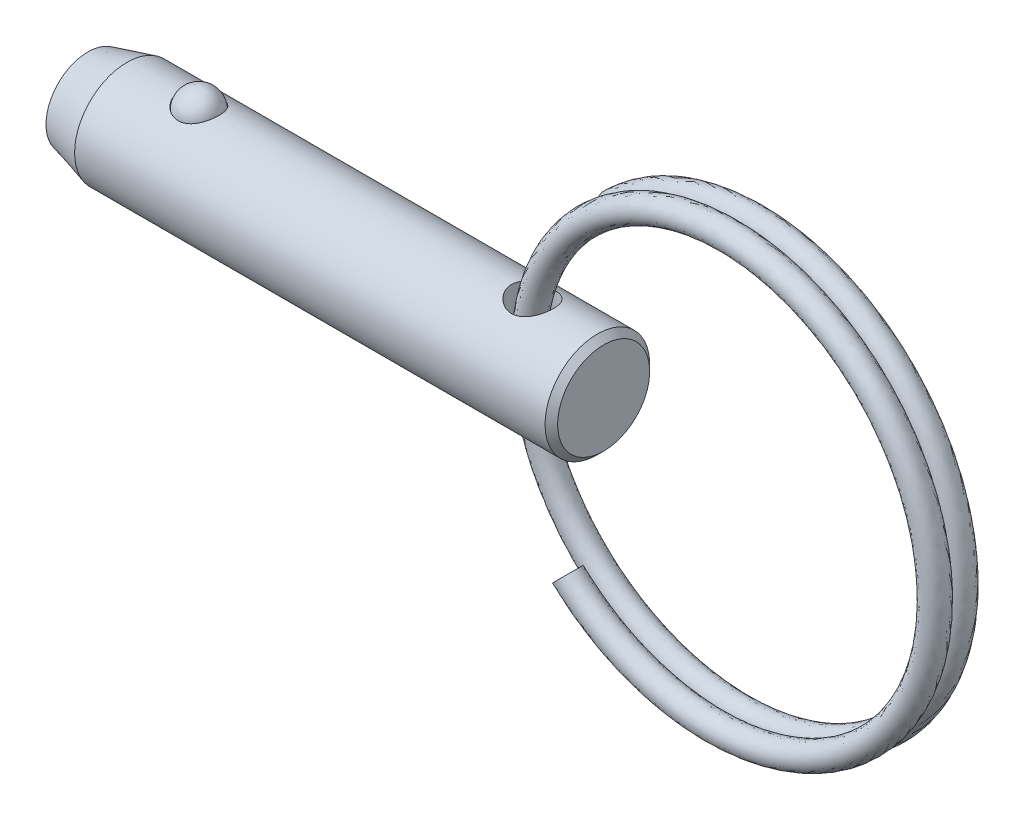
SolidWorks part; units mm, degrees
ref_plane "Front" through (0, 0, 0) normal (0, 0, 1) x (1, 0, 0)
ref_plane "Top" through (0, 0, 0) normal (0, 1, 0) x (1, 0, 0)
ref_plane "Right" through (0, 0, 0) normal (1, 0, 0) x (0, 0, -1)
sketch "Sketch1" plane through (0, 0, 0) normal (0, 0, 1) x (1, 0, 0)
  line L0 (15.6464, 2.794) -> (15.2654, 3.175)
  line L1 (15.2654, 3.175) -> (15.6464, 3.175) construction
  line L4 (15.6464, 2.794) -> (15.6464, 0)
  line L5 (15.6464, 3.175) -> (15.6464, 2.794) construction
  line L16 (15.2654, 3.175) -> (-13.2765, 3.175)
  line L17 (-15.6464, 3.175) -> (-15.6464, 2.54) construction
  line L19 (-13.2765, 3.175) -> (-15.6464, 3.175) construction
  line L22 (-15.6464, -3.175) -> (-13.2765, -3.175) construction
  line L23 (-8.9119, 2.8575) -> (-8.9119, -2.8575) construction
  line L24 (-15.6464, 0) -> (15.6464, 0)
  line L27 (15.6464, 0) -> (18.4404, 0) construction
  line L29 (-15.6464, 0) -> (-15.6464, -2.54) construction
  line L36 (10.0584, 0) -> (10.0584, 3.175) construction
  line L37 (-15.6464, 2.54) -> (-15.6464, 0)
  line L38 (-13.2765, -3.175) -> (15.6464, -3.175) construction
  line L39 (-15.6464, -2.54) -> (-15.6464, -3.175) construction
  line L40 (-13.2765, 3.175) -> (-15.6464, 2.54)
  line L42 (-13.2765, -3.175) -> (-15.6464, -2.54) construction
  line L43 (-13.2765, 3.175) -> (-13.2765, -3.175) construction
  circle A2 centre (-8.9119, 2.8575) radius 1.2319 construction
  point P35 (-7.7216, 3.175)
  dimension "A1" = 15
revolve "Revolve1" add sketch "Sketch1" angle 360 about L27
sketch "Sketch2" plane through (0, 0, 0) normal (0, 0, 1) x (1, 0, 0)
  line L0 (-7.6546, 2.8575) -> (-10.1692, 2.8575)
  line L1 (-8.9119, 4.0894) -> (-8.9119, 4.1148) construction
  line L2 (-7.6546, 2.8575) -> (-5.14, 2.8575) construction
  circle A0 centre (-8.9119, 2.8575) radius 1.2319 construction
  circle A1 centre (-8.9119, 2.8575) radius 1.2319 construction
  arc A2 (-10.1692, 2.8575) -> (-7.6546, 2.8575) centre (-8.9119, 2.8575) cw
  dimension "D1" = 0.0254
revolve "Cut-Revolve1" cut sketch "Sketch2" angle 360 about L2
sketch "Sketch3" plane through (0, 0, 0) normal (0, 0, 1) x (1, 0, 0)
  line L0 (-7.68, 2.8575) -> (-10.1438, 2.8575)
  line L1 (-7.68, 2.8575) -> (-5.2162, 2.8575) construction
  circle A0 centre (-8.9119, 2.8575) radius 1.2319 construction
  arc A1 (-7.68, 2.8575) -> (-10.1438, 2.8575) centre (-8.9119, 2.8575) ccw
revolve "Revolve2" add sketch "Sketch3" angle 360 about L1
sketch "Sketch4" plane through (0, 0, 0) normal (0, 0, 1) x (1, 0, 0)
  line L1 (11.3284, -3.175) -> (12.5984, -3.175)
  line L2 (11.3284, -3.175) -> (11.3284, 3.175)
  line L3 (11.3284, 3.175) -> (12.5984, 3.175)
  line L4 (12.5984, -3.175) -> (12.5984, 3.175)
  line L5 (11.3284, -3.175) -> (11.3284, -4.445) construction
  line L6 (12.5984, 3.175) -> (15.6464, 3.175) construction
  line L8 (10.0584, -3.175) -> (10.0584, 3.175) construction
  line L9 (10.0584, 0) -> (11.3284, 0) construction
  line L11 (11.3284, 0) -> (12.5984, 0) construction
  line L12 (15.2654, 3.175) -> (-13.2765, 3.175) construction
  line L14 (-13.2765, -3.175) -> (15.6464, -3.175) construction
  dimension "D1" = 2.54
revolve "Cut-Revolve2" cut sketch "Sketch4" angle 360 about L2
sketch "Sketch5" plane through (0, 0, 0) normal (0, 0, 1) x (1, 0, 0)
  line L0 (0, 0) -> (10.3514, 0) construction
  line L1 (10.3514, 0) -> (10.3514, 3.175) construction
  line L2 (15.2654, 3.175) -> (-13.2765, 3.175) construction
  line L3 (23.8134, 0) -> (37.2754, 0) construction
  line L4 (12.5984, 3.175) -> (12.3054, 3.175) construction
  line L5 (11.3284, 3.175) -> (12.5984, 3.175) construction
  line L6 (10.7312, 3.175) -> (10.7312, -3.175) construction
  line L7 (10.3514, 3.175) -> (10.0584, 3.175) construction
  line L8 (11.3284, -3.175) -> (12.5984, -3.175) construction
  line L9 (10.7312, -3.175) -> (12.5984, -3.175) construction
  line L10 (10.3514, 0) -> (23.8134, 0) construction
  line L12 (12.3054, 3.175) -> (10.7312, 3.175) construction
  line L13 (23.8134, 11.938) -> (23.8134, 13.462) construction
  circle A0 centre (23.8134, 0) radius 13.462
  circle A1 centre (23.8134, 0) radius 11.938 construction
  circle A2 centre (23.8134, 0) radius 12.7 construction
  point P26 (23.8134, 12.7)
curve "Helix/Spiral1" pitch 1.5494 height 1.3557 radius 13.462 left hand yes centre (23.8134, 0, 0) axis (0, 0, -1) start towards (1, 0, 0)
sketch "Sketch6" plane through (114.0038, 0, 0) normal (0, 1, 0) x (0, 0, -1)
  line L0 (0, 102.1284) -> (0, 102.8904) construction
  line L1 (0, 102.8904) -> (0, 103.6524) construction
  circle A0 centre (0, 102.8904) radius 0.762
  dimension "D1" = 1.524
sketch "Sketch7" plane through (0, 0, 0) normal (0, 0, 1) x (1, 0, 0)
  circle A0 centre (23.8134, 0) radius 13.462 construction
  circle A1 centre (23.8134, 0) radius 13.462
curve "Helix/Spiral2" pitch 1.5494 height 1.3557 radius 13.462 left hand yes centre (23.8134, 0, 0) axis (0, 0, 1) start towards (1, 0, 0)
sweep "Sweep1" add profiles "Sketch6" path "Helix/Spiral1"
sweep "Sweep2" add profiles "Sketch6<2>" path "Helix/Spiral2"
sketch "Sketch6<2>" plane through (114.0038, 0, 0) normal (0, 1, 0) x (0, 0, -1) same geometry as "Sketch6"
equation "\"D12@Sketch1\"=\"A@Sketch1\" * 0.80"
equation "\"D2@Sketch1\"=\"A@Sketch1\" * 0.9"
equation "\"D1@Sketch4\" = \"A@Sketch1\" / 2.5"
equation "\"Ring OD@Sketch5\" = \"R Ring Dia@Sketch5\" * 0.06"
equation "\"D4@Helix/Spiral1\"=\"Ring OD@Sketch5\" + 0.001"
equation "\"D1@Sketch6\"=\"Ring OD@Sketch5\""
equation "\"D4@Helix/Spiral2\" = \"D4@Helix/Spiral1\""
equation "\"D5@Helix/Spiral2\" = \"D5@Helix/Spiral1\""
